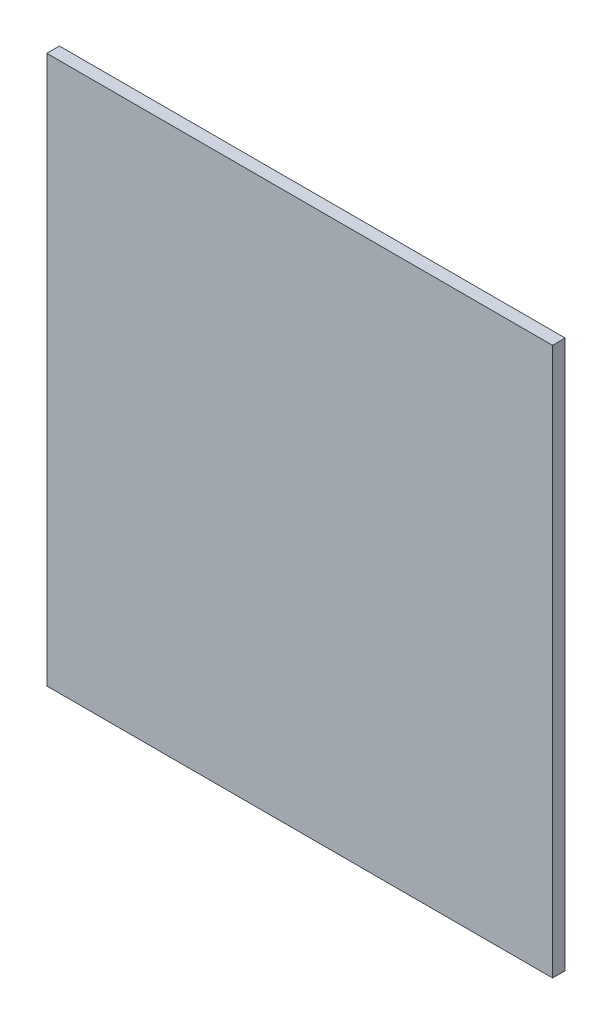
SolidWorks part; units mm, degrees
ref_plane "前视基准面" through (0, 0, 0) normal (0, 0, 1) x (1, 0, 0)
ref_plane "上视基准面" through (0, 0, 0) normal (0, 1, 0) x (1, 0, 0)
ref_plane "右视基准面" through (0, 0, 0) normal (1, 0, 0) x (0, 0, -1)
other "Configuration Table"
sketch "草图1" plane through (0, 0, 0) normal (0, 0, 1) x (1, 0, 0)
  line L1 (60, -65) -> (-60, -65)
  line L2 (60, -65) -> (60, 65)
  line L3 (60, 65) -> (-60, 65)
  line L4 (-60, -65) -> (-60, 65)
  line L5 (60, -65) -> (-60, 65) construction
  line L6 (60, 65) -> (-60, -65) construction
  point P0 (0, 0)
  dimension "D1" = 120
  dimension "D2" = 130
extrude "凸台-拉伸1" add sketch "草图1" along normal blind 3
